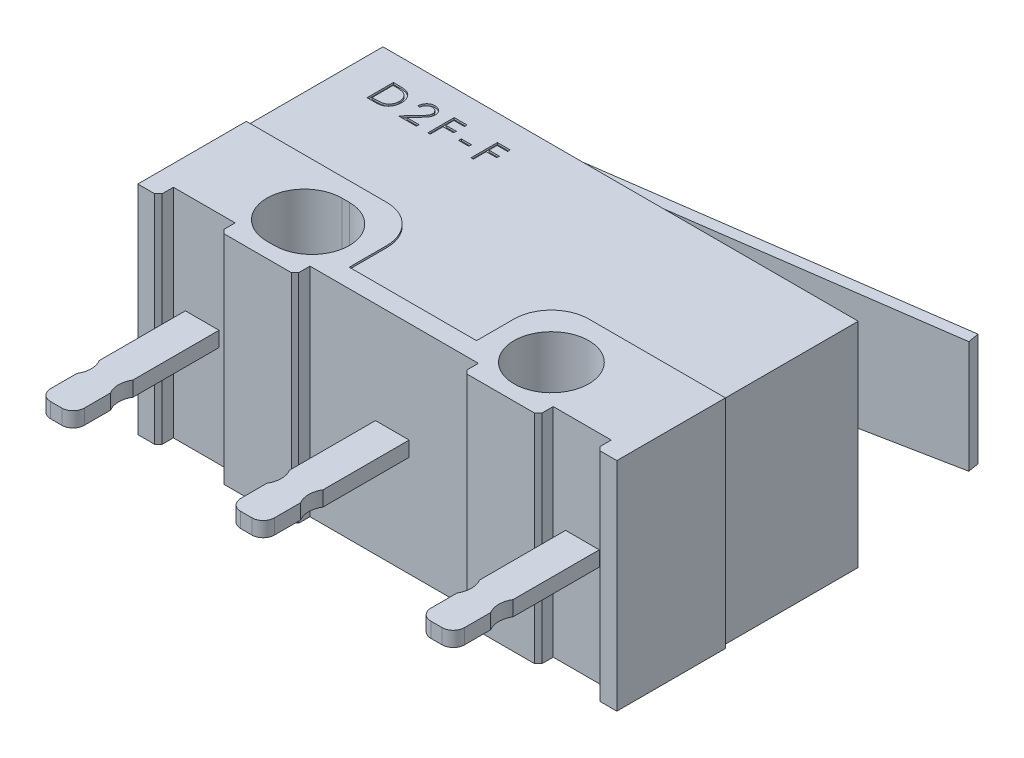
SolidWorks part; units mm, degrees
ref_plane "Front" through (0, 0, 0) normal (0, 0, 1) x (1, 0, 0)
ref_plane "Top" through (0, 0, 0) normal (0, 1, 0) x (1, 0, 0)
ref_plane "Right" through (0, 0, 0) normal (1, 0, 0) x (0, 0, -1)
sketch "Sketch1" plane through (0, 0, 0) normal (0, 1, 0) x (1, 0, 0)
  line L0 (12.7, 6.1) -> (0, 6.1)
  line L1 (0, 0) -> (12.7, 0)
  line L2 (0, 0) -> (0, 6.1)
  line L4 (12.7, 0) -> (12.7, 6.1)
  dimension "D1" = 12.7
  dimension "D3" = 6.1
extrude "Base-Extrude" add sketch "Sketch1" along normal blind 5.7
sketch "Sketch2" plane through (0, 5.7, 0) normal (0, 1, 0) x (-1, 0, 0)
  line L2 (0, -6.1) -> (0, 0) construction
  line L4 (0, 0) -> (-12.7, 0) construction
  line L6 (-3, -2.001) -> (-3.2, -2.001)
  line L7 (-3.1, -4.6917) -> (-3.1, -0.5241) construction
  line L8 (-3, -0.001) -> (-3.2, -0.001)
  arc A0 (-3.2, -2.001) -> (-3.2, -0.001) centre (-3.2, -1.001) cw
  circle A1 centre (-9.6, -1.001) radius 1
  arc A2 (-3, -2.001) -> (-3, -0.001) centre (-3, -1.001) ccw
  dimension "D1" = 2
  dimension "D2" = 2.2
  dimension "D3" = 1.001
  dimension "D4" = 6.5
  dimension "D5" = 3.1
extrude "Cut-Extrude1" cut sketch "Sketch2" against normal through all
sketch "Sketch3" plane through (0, 5.7, 0) normal (0, 1, 0) x (-1, 0, 0)
  line L0 (-3, -0.001) -> (-3.2, -0.001) construction
  line L1 (-12.7, -2.501) -> (-9.1, -2.501)
  line L2 (-12.7, 0) -> (-12.7, -6.1) construction
  line L3 (-4.7, -1.501) -> (-4.7, -0.5)
  line L4 (-8.1, -0.5) -> (-4.7, -0.5)
  line L5 (-8.1, -0.5) -> (-8.1, -1.501)
  line L6 (-3.7, -2.501) -> (0, -2.501)
  line L7 (-3.2, -2.001) -> (-3, -2.001) construction
  line L8 (-3, -0.001) -> (-3.2, -0.001)
  line L9 (0, -6.1) -> (0, 0) construction
  line L10 (0, -2.501) -> (0, 0)
  line L11 (0, 0) -> (-12.7, 0)
  line L12 (-12.7, 0) -> (-12.7, -2.501)
  line L13 (-6.35, -6.1) -> (-6.35, -2.9124) construction
  line L14 (-12.7, -6.1) -> (0, -6.1) construction
  line L15 (-3.2, -2.001) -> (-3, -2.001)
  arc A0 (-3.2, -0.001) -> (-3.2, -2.001) centre (-3.2, -1.001) ccw construction
  circle A1 centre (-9.6, -1.001) radius 1 construction
  arc A2 (-3, -2.001) -> (-3, -0.001) centre (-3, -1.001) ccw construction
  arc A3 (-3, -2.001) -> (-3, -0.001) centre (-3, -1.001) ccw
  arc A4 (-3.2, -0.001) -> (-3.2, -2.001) centre (-3.2, -1.001) ccw
  circle A5 centre (-9.6, -1.001) radius 1
  arc A16 (-9.1, -2.501) -> (-8.1, -1.501) centre (-9.1, -1.501) ccw
  arc A17 (-4.7, -1.501) -> (-3.7, -2.501) centre (-3.7, -1.501) ccw
  point P5 (-3.2, -1.001)
  point P16 (-9.6, -1.001)
  dimension "D1" = 1
  dimension "D3" = 0.5
  dimension "D4" = 1
  dimension "D2" = 0.5
  dimension "D5" = 0.5
  dimension "D6" = 0.5
  dimension "D7" = 0.5
extrude "Boss-Extrude1" add sketch "Sketch3" along normal blind 0.05
sketch "Sketch4" plane through (0, 0, 0) normal (0, -1, 0) x (1, 0, 0)
  line L2 (3, -0.001) -> (3.2, -0.001) construction
  line L3 (3.2, -2.001) -> (3, -2.001) construction
  line L4 (3, -0.001) -> (3.2, -0.001)
  line L5 (3.2, -2.001) -> (3, -2.001)
  line L10 (12.7, -2.501) -> (12.7, 0)
  line L11 (9.1, -2.501) -> (12.7, -2.501)
  line L12 (8.1, -0.5) -> (8.1, -1.501)
  line L13 (4.7, -0.5) -> (8.1, -0.5)
  line L14 (4.7, -1.501) -> (4.7, -0.5)
  line L15 (0, -2.501) -> (3.7, -2.501)
  line L16 (0, 0) -> (0, -2.501)
  line L17 (12.7, 0) -> (0, 0)
  line L18 (12.7, -2.501) -> (12.7, 0)
  line L19 (9.1, -2.501) -> (12.7, -2.501)
  line L20 (8.1, -0.5) -> (8.1, -1.501)
  line L21 (4.7, -0.5) -> (8.1, -0.5)
  line L22 (4.7, -1.501) -> (4.7, -0.5)
  line L23 (0, -2.501) -> (3.7, -2.501)
  line L24 (0, 0) -> (0, -2.501)
  line L25 (12.7, 0) -> (0, 0)
  circle A1 centre (9.6, -1.001) radius 1 construction
  circle A2 centre (9.6, -1.001) radius 1
  arc A3 (8.1, -1.501) -> (9.1, -2.501) centre (9.1, -1.501) ccw
  arc A4 (3.7, -2.501) -> (4.7, -1.501) centre (3.7, -1.501) ccw
  arc A5 (8.1, -1.501) -> (9.1, -2.501) centre (9.1, -1.501) ccw
  arc A6 (3.7, -2.501) -> (4.7, -1.501) centre (3.7, -1.501) ccw
  arc A9 (3, -0.001) -> (3, -2.001) centre (3, -1.001) ccw construction
  arc A10 (3.2, -2.001) -> (3.2, -0.001) centre (3.2, -1.001) ccw construction
  arc A11 (3, -0.001) -> (3, -2.001) centre (3, -1.001) ccw
  arc A12 (3.2, -2.001) -> (3.2, -0.001) centre (3.2, -1.001) ccw
  dimension "D1" = 0
extrude "Boss-Extrude2" add sketch "Sketch4" along normal blind 0.05
sketch "Sketch13" plane through (0, 0, -6.1) normal (0, 0, -1) x (-1, 0, 0)
  line L0 (-4.4, 1.1185) -> (-4.4, 4.8941) construction
  line L1 (0, 5.7) -> (0, 0) construction
  line L2 (0, 2.85) -> (-6.3505, 2.85) construction
  line L3 (-3.8, 1.4) -> (-5, 1.4)
  line L4 (-3.8, 1.4) -> (-3.8, 4.3)
  line L5 (-3.8, 4.3) -> (-5, 4.3)
  line L6 (-5, 1.4) -> (-5, 4.3)
  dimension "D1" = 4.4
  dimension "D2" = 2.9
  dimension "D3" = 1.2
extrude "Extrude1" add sketch "Sketch13" along normal blind 0.5
fillet "Fillet1" radius 0.599 2 edges at (3.8, 2.85, -6.6) (5, 2.85, -6.6)
sketch "Sketch6" plane through (0, 0, 0) normal (0, 0, 1) x (1, 0, 0)
  line L0 (19.8, 2.85) -> (0, 2.85) construction
  line L3 (0, 5.75) -> (12.7, 5.75) construction
  line L4 (0.82, 3.05) -> (1.72, 3.05)
  line L5 (0.82, 3.05) -> (0.82, 2.65)
  line L6 (0.82, 2.65) -> (1.72, 2.65)
  line L7 (1.72, 3.05) -> (1.72, 2.65)
  line L8 (5.9, 3.05) -> (6.8, 3.05)
  line L9 (5.9, 3.05) -> (5.9, 2.65)
  line L10 (5.9, 2.65) -> (6.8, 2.65)
  line L11 (6.8, 3.05) -> (6.8, 2.65)
  line L12 (12.7, -0.05) -> (0, -0.05) construction
  line L13 (10.98, 3.05) -> (11.88, 3.05)
  line L14 (10.98, 3.05) -> (10.98, 2.65)
  line L15 (10.98, 2.65) -> (11.88, 2.65)
  line L16 (11.88, 3.05) -> (11.88, 2.65)
  line L17 (6.35, 5.5596) -> (6.35, 0.4807) construction
  line L18 (0, 5.75) -> (0, -0.05) construction
  line L19 (12.7, 5.75) -> (12.7, -0.05) construction
  line L20 (1.27, 3.8866) -> (1.27, 2.1836) construction
  line L21 (11.43, 3.8866) -> (11.43, 2.1836) construction
  dimension "D1" = 0.4
  dimension "D2" = 0.9
  dimension "D3" = 0.9
  dimension "D4" = 0.9
  dimension "D5" = 5.08
  dimension "D6" = 5.08
extrude "Boss-Extrude4" add sketch "Sketch6" along normal blind 3.9
sketch "Sketch14" plane through (0, 3.05, 0) normal (0, 1, 0) x (-1, 0, 0)
  line L1 (-6.8, 2.3) -> (-6.8, 2.9)
  line L2 (-6.8, 3.9) -> (-5.9, 3.9) construction
  line L3 (-6.8, 3.9) -> (-6.8, 0) construction
  line L4 (-6.35, 3.9) -> (-6.35, 1.5338) construction
  line L5 (-5.9, 2.3) -> (-5.9, 2.9)
  line L6 (-1.72, 2.3) -> (-1.72, 2.9)
  line L7 (-1.27, 3.9404) -> (-1.27, 1.4741) construction
  line L8 (-0.82, 2.3) -> (-0.82, 2.9)
  line L9 (-0.82, 3.9) -> (-0.82, 0) construction
  line L10 (-1.72, 3.9) -> (-1.72, 0) construction
  line L11 (-1.72, 3.9) -> (-0.82, 3.9) construction
  line L12 (-11.88, 2.3) -> (-11.88, 2.9)
  line L13 (-10.98, 2.3) -> (-10.98, 2.9)
  arc A0 (-6.8, 2.3) -> (-6.8, 2.9) centre (-7.3, 2.6) ccw
  arc A1 (-5.9, 2.3) -> (-5.9, 2.9) centre (-5.4, 2.6) cw
  arc A2 (-1.72, 2.3) -> (-1.72, 2.9) centre (-2.22, 2.6) ccw
  arc A3 (-0.82, 2.3) -> (-0.82, 2.9) centre (-0.32, 2.6) cw
  arc A4 (-11.88, 2.3) -> (-11.88, 2.9) centre (-12.38, 2.6) ccw
  arc A5 (-10.98, 2.3) -> (-10.98, 2.9) centre (-10.48, 2.6) cw
  dimension "D1" = 1.6
  dimension "D2" = 1
  dimension "D3" = 0.5
  dimension "D4" = 0.5
  dimension "D5" = 1
extrude "Cut-Extrude4" cut sketch "Sketch14" against normal through all
fillet "Fillet2" radius 0.3 6 edges at (10.98, 2.85, 3.9) (5.9, 2.85, 3.9) (0.82, 2.85, 3.9) (1.72, 2.85, 3.9) (11.88, 2.85, 3.9) (6.8, 2.85, 3.9)
sketch "Sketch8" plane through (0, 0, 0) normal (0, 0, 1) x (1, 0, 0)
  line L0 (12.2, 5.75) -> (12.2, -0.05)
  line L1 (0.5, 5.75) -> (0.5, -0.05)
  line L2 (2.15, 5.75) -> (2.15, -0.05)
  line L3 (4.15, 5.75) -> (4.15, -0.05)
  line L4 (0, 5.75) -> (0, -0.05)
  line L5 (0, 5.75) -> (0, -0.05)
  line L6 (0, -0.05) -> (12.7, -0.05)
  line L7 (0, -0.05) -> (0.5, -0.05)
  line L8 (12.7, -0.05) -> (12.7, 5.75)
  line L9 (12.7, -0.05) -> (12.7, 5.75)
  line L10 (12.7, 5.75) -> (0, 5.75)
  line L11 (12.7, 5.75) -> (12.2, 5.75)
  line L12 (8.65, 5.75) -> (8.65, -0.05)
  line L13 (10.65, 5.75) -> (10.65, -0.05)
  line L14 (3.15, 5.2233) -> (3.15, 1.4338) construction
  line L15 (9.65, 4.3755) -> (9.65, 2.0048) construction
  line L16 (0.5, 5.75) -> (0, 5.75)
  line L17 (2.15, -0.05) -> (4.15, -0.05)
  line L18 (4.15, 5.75) -> (2.15, 5.75)
  line L19 (10.65, 5.75) -> (8.65, 5.75)
  line L20 (8.65, -0.05) -> (10.65, -0.05)
  line L21 (12.2, -0.05) -> (12.7, -0.05)
  dimension "D2" = 0.5
  dimension "D3" = 0.5
  dimension "D4" = 3.15
  dimension "D5" = 2
  dimension "D6" = 2
  dimension "D7" = 6.5
  dimension "D1" = 0
extrude "Boss-Extrude5" add sketch "Sketch8" along normal blind 0.4
chamfer "Chamfer3" distance 0.1 angle 45 6 edges at (12.2, 2.85, 0.4) (10.65, 2.85, 0.4) (8.65, 2.85, 0.4) (4.15, 2.85, 0.4) (2.15, 2.85, 0.4) (0.5, 2.85, 0.4)
ref_plane "Plane1" through (0, 3, 0) normal (0, 1, 0) x (-1, 0, 0)
sketch "Sketch11" plane through (0, 3, 0) normal (0, 1, 0) x (-1, 0, 0)
  line L0 (-13.4, -8.6) -> (-1.1504, -6.5459)
  line L1 (-0.9, -6.25) -> (-0.9, -6.1)
  line L2 (-12.7, -6.1) -> (0, -6.1) construction
  line L3 (-1.2, -6.1654) -> (-1.2, -6.1)
  line L4 (-13.4496, -8.3041) -> (-1.2835, -6.264)
  line L5 (-10.55, 0.4) -> (-8.75, 0.4) construction
  line L6 (-1.2, -6.1) -> (-0.9, -6.1)
  line L7 (-13.4, -8.6) -> (-13.4496, -8.3041)
  line L8 (0, -6.1) -> (0, -2.501) construction
  line L9 (0, -6.1) -> (0, -2.501) construction
  arc A0 (-1.1504, -6.5459) -> (-0.9, -6.25) centre (-1.2, -6.25) ccw
  circle A1 centre (-9.6, -1.001) radius 1 construction
  arc A2 (-1.2, -6.1654) -> (-1.2835, -6.264) centre (-1.3, -6.1654) cw
  point P12 (-9.6, -1.001)
  point P19 (-1.2, -6.25)
  dimension "D1" = 0.3
  dimension "D3" = 0.15
  dimension "D7" = 0.1
  dimension "D4" = 13.4
  dimension "D5" = 0.9
  dimension "D6" = 9
  dimension "D2" = 0.3
extrude "Boss-Extrude6" add sketch "Sketch11" along normal blind 1.8 and the other way blind 1.8
sketch "Sketch15" plane through (0, 0, -6.1) normal (0, 0, -1) x (-1, 0, 0)
  line L2 (-13.4, 3) -> (-12.6228, 3) construction
  line L3 (-13.4, 4.8) -> (-13.4, 1.2) construction
  line L4 (-0.9, 1.2) -> (-13.4496, 1.2)
  line L5 (-13.4496, 1.2) -> (-13.4496, 1.5)
  line L6 (-13.4496, 4.5) -> (-13.4496, 4.8)
  line L7 (-13.4496, 4.8) -> (-0.9, 4.8)
  line L9 (-13.4496, 1.5) -> (-0.9, 1.2)
  line L11 (-0.9, 4.8) -> (-13.4496, 4.5)
  dimension "D1" = 3
extrude "Cut-Extrude5" cut sketch "Sketch15" along normal through all
sketch "Sketch12" plane through (-12.4971, 5.7, -3.2914) normal (0, 1, 0) x (1, 0, 0)
  text T0 "D2F-F" font "Century Gothic" height in points 2
extrude "Cut-Extrude3" cut sketch "Sketch12" against normal blind 0.05
sketch "Sketch16" plane through (12.7, 0, 0) normal (1, 0, 0) x (0, 0, -1)
  line L1 (-0.4, 5.75) -> (2.501, 5.75)
  line L2 (-0.4, 5.75) -> (-0.4, -0.05)
  line L3 (-0.4, -0.05) -> (2.501, -0.05)
  line L4 (2.501, 5.75) -> (2.501, -0.05)
extrude "Extrude2" add sketch "Sketch16" along normal blind 0.05
sketch "Sketch17" plane through (0, 0, 0) normal (-1, 0, 0) x (0, 0, 1)
  line L1 (0.4, -0.05) -> (-2.501, -0.05)
  line L2 (0.4, -0.05) -> (0.4, 5.75)
  line L3 (0.4, 5.75) -> (-2.501, 5.75)
  line L4 (-2.501, -0.05) -> (-2.501, 5.75)
extrude "Extrude3" add sketch "Sketch17" along normal blind 0.05
sketch "Sketch18" plane through (0, 5.75, 0) normal (0, 1, 0) x (-1, 0, 0)
  line L0 (0, -8.8) -> (-13.4634, -8.8)
  line L1 (-10.55, 0.4) -> (-8.75, 0.4) construction
  line L2 (0, -8.1) -> (-13.4634, -8.1)
  line L3 (0, -6.1) -> (0, -2.501) construction
  line L4 (0, -6.6) -> (-13.4634, -6.6)
  dimension "D1" = 9.2
  dimension "D2" = 8.5
  dimension "D3" = 7
sketch "Sketch19" plane through (-1.0362, 0, -6.1792) normal (-0.1654, 0, -0.9862) x (-0.9862, 0, 0.1654)
  line L0 (-1.9212, 2.25) -> (-7.3319, 2.5005)
  line L1 (-1.9212, 3.75) -> (-7.3319, 3.4995)
  line L2 (-1.9212, 3) -> (-9.9712, 3) construction
  line L3 (-1.9212, 4.8) -> (-1.9212, 1.2) construction
  line L4 (-1.9212, 3.75) -> (-1.9212, 2.25)
  line L5 (-1.0088, 5.7) -> (-1.0088, 0) construction
  arc A0 (-7.3319, 3.4995) -> (-7.3319, 2.5005) centre (-7.3088, 3) ccw
  dimension "D1" = 0.5
  dimension "D2" = 6.8
  dimension "D3" = 1.5
extrude "Cut-Extrude6" cut sketch "Sketch19" against normal up to surface (0.3 mm away) up to face at (7.3665, 3, -7.2841)
sketch "Sketch20" plane through (0, 5.75, 0) normal (0, 1, 0) x (1, 0, 0)
  line L1 (3.2, 2.001) -> (3, 2.001) construction
  line L2 (3.1, 2.001) -> (3.1, 0.6306) construction
  line L3 (2, 1.001) -> (3.338, 1.001) construction
  circle A0 centre (3.1, 1.001) radius 0.8449
  arc A1 (3, 2.001) -> (3, 0.001) centre (3, 1.001) ccw construction
sketch "Sketch21" plane through (0, 0, 3.9) normal (0, 0, 1) x (1, 0, 0)
  line L0 (1.42, 3.05) -> (1.12, 3.05) construction
  line L1 (0.82, 2.65) -> (1.72, 2.65) construction
  line L2 (1.27, 2.85) -> (1.27, 3.3038) construction
  line L3 (1.42, 2.65) -> (1.42, 3.05) construction
  line L4 (1.12, 3.05) -> (1.12, 2.65) construction
  line L5 (6.2, 2.65) -> (6.5, 2.65) construction
  line L6 (6.5, 3.05) -> (6.2, 3.05) construction
  line L7 (6.35, 2.85) -> (6.35, 3.1949) construction
  line L8 (6.5, 2.65) -> (6.5, 3.05) construction
  line L9 (6.2, 3.05) -> (6.2, 2.65) construction
  circle A0 centre (1.27, 2.85) radius 0.2
  circle A1 centre (6.35, 2.85) radius 0.2
sketch "Sketch22" plane through (-1.0362, 0, -6.1792) normal (-0.1654, 0, -0.9862) x (-0.9862, 0, 0.1654)
  line L0 (-11.9475, 3) -> (-4.4049, 3) construction
  line L1 (-2.2171, 1.206) -> (-14.6378, 1.4988) construction
  line L2 (-14.6378, 4.5012) -> (-2.2171, 4.794) construction
  line L3 (-7.4767, 3.3697) -> (-2.2171, 3.4937)
  line L4 (-2.2171, 3.4937) -> (-2.2171, 2.5063)
  line L5 (-2.2171, 2.5063) -> (-7.4767, 2.6303)
  line L6 (-14.6378, 4.5012) -> (-14.6378, 1.4988) construction
  line L7 (-2.2171, 4.794) -> (-2.2171, 3.7363) construction
  arc A0 (-7.4767, 3.3697) -> (-7.4767, 2.6303) centre (-7.468, 3) ccw
  dimension "D1" = 6.8
  dimension "D2" = 1.3
extrude "Cut-Extrude7" [suppressed] cut sketch "Sketch22" against normal up to surface (0.3 mm away)
